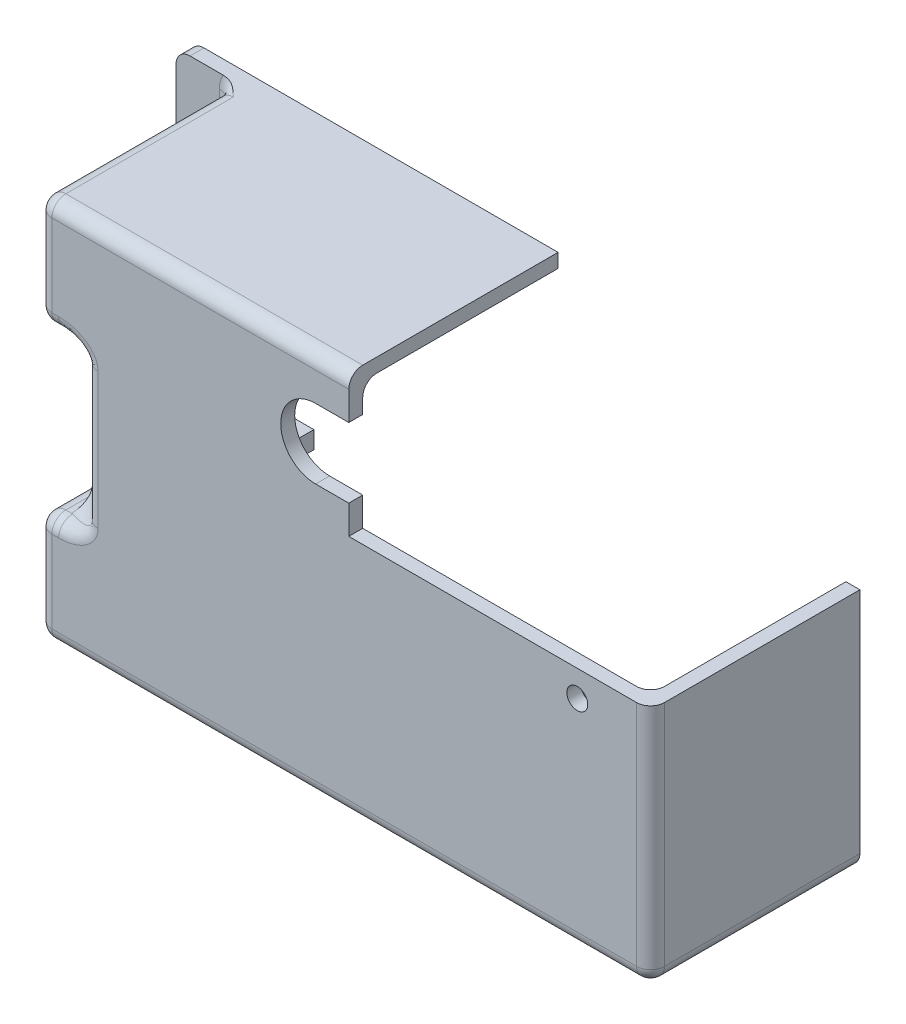
SolidWorks part; units mm, degrees
material "3D_printed_PLA"
ref_plane "Front Plane" through (0, 0, 0) normal (0, 0, 1) x (1, 0, 0)
ref_plane "Top Plane" through (0, 0, 0) normal (0, 1, 0) x (1, 0, 0)
ref_plane "Right Plane" through (0, 0, 0) normal (1, 0, 0) x (0, 0, -1)
sketch "Sketch1" plane through (0, 0, 0) normal (0, 0, 1) x (1, 0, 0)
  line L1 (-48, -27.5) -> (48, -27.5)
  line L2 (-48, -27.5) -> (-48, 27.5)
  line L3 (-48, 27.5) -> (48, 27.5)
  line L4 (48, -27.5) -> (48, 27.5)
  line L5 (-48, -27.5) -> (48, 27.5) construction
  line L6 (-48, 27.5) -> (48, -27.5) construction
  point P0 (0, 0)
  dimension "D1" = 96
  dimension "D2" = 55
extrude "Boss-Extrude1" add sketch "Sketch1" along normal blind 2
sketch "Sketch2" plane through (0, 0, 0) normal (0, 0, -1) x (-1, 0, 0)
  line L0 (-46, 25.5) -> (-46, -25.5)
  line L1 (-46, -25.5) -> (46, -25.5)
  line L2 (46, -25.5) -> (46, 25.5)
  line L3 (46, 25.5) -> (-46, 25.5)
  line L4 (-48, 27.5) -> (-48, -27.5)
  line L5 (-48, -27.5) -> (48, -27.5)
  line L6 (48, -27.5) -> (48, 27.5)
  line L7 (48, 27.5) -> (-48, 27.5)
  line L8 (-48, 27.5) -> (-48, -27.5)
  line L9 (-48, -27.5) -> (48, -27.5)
  line L10 (48, -27.5) -> (48, 27.5)
  line L11 (48, 27.5) -> (-48, 27.5)
  dimension "D1" = 0
  dimension "D2" = 2
extrude "Boss-Extrude2" add sketch "Sketch2" along normal blind 28
sketch "Sketch5" plane through (0, 0, 2) normal (0, 0, 1) x (1, 0, 0)
  line L0 (-48, 11.75) -> (-30, 11.75)
  line L1 (-48, 27.5) -> (-48, -27.5) construction
  line L2 (-30, 11.75) -> (-30, 14.25)
  line L3 (-30, 14.25) -> (-39, 14.25)
  line L4 (-39, 14.25) -> (-39, 27.5)
  line L5 (48, 27.5) -> (-48, 27.5) construction
  line L6 (-39, 27.5) -> (-48, 27.5)
  line L7 (-48, 27.5) -> (-48, 11.75)
  line L8 (-46, 0) -> (-39.8001, 0) construction
  line L9 (-46, -25.5) -> (-46, 25.5) construction
  line L10 (-39, -27.5) -> (-48, -27.5)
  line L11 (-39, -14.25) -> (-39, -27.5)
  line L12 (-30, -14.25) -> (-39, -14.25)
  line L13 (-30, -11.75) -> (-30, -14.25)
  line L14 (-48, -11.75) -> (-30, -11.75)
  line L15 (-48, -27.5) -> (-48, -11.75)
  dimension "D1" = 15.75
  dimension "D2" = 18
  dimension "D3" = 2.5
  dimension "D4" = 9
extrude "Boss-Extrude3" add sketch "Sketch5" against normal offset from surface (29.75 mm away) 0.25 up to face at (0, 0, -28)
sketch "Sketch6" plane through (0, 0, 2) normal (0, 0, 1) x (1, 0, 0)
  line L0 (-46, -11.75) -> (-30, -11.75) construction
  line L1 (-30, 11.75) -> (-37, 11.75)
  line L2 (-30, 11.75) -> (-30, -11.75)
  line L3 (-30, -11.75) -> (-37, -11.75)
  line L4 (-37, 11.75) -> (-37, -11.75)
  dimension "D1" = 7
extrude "Boss-Extrude4" add sketch "Sketch6" against normal blind 5.75
sketch "Sketch7" plane through (-48, 0, 0) normal (-1, 0, 0) x (0, 0, 1)
  line L0 (2, 27.5) -> (2, -27.5) construction
  line L1 (2, -11.75) -> (-28, -11.75)
  line L2 (2, -11.75) -> (2, 11.75)
  line L3 (2, 11.75) -> (-28, 11.75)
  line L4 (-28, -11.75) -> (-28, 11.75)
  line L5 (-28, -27.5) -> (-28, 27.5) construction
  line L6 (-28, 27.5) -> (2, 0) construction
  line L7 (2, 0) -> (-28, -27.5) construction
  line L8 (0, 11.75) -> (-27.75, 11.75) construction
extrude "Cut-Extrude2" cut sketch "Sketch7" against normal up to vertex
sketch "Sketch8" plane through (0, -27.5, 0) normal (0, -1, 0) x (1, 0, 0)
  line L0 (48, -28) -> (-48, -28) construction
  line L1 (-48, 2) -> (-39.8, 2)
  line L2 (-48, 2) -> (-48, -26)
  line L3 (-48, -26) -> (-39.8, -26)
  line L4 (-39.8, 2) -> (-39.8, -26)
  line L5 (-39, 0) -> (-39, -27.75) construction
  dimension "D1" = 2
  dimension "D2" = 0.8
extrude "Cut-Extrude3" cut sketch "Sketch8" against normal through all both and the other way through all
chamfer "Chamfer1" distance 5 angle 45 1 edges at (-37, 0, 2)
fillet "Fillet1" radius 2 32 edges at (3.5, -25.5, 0) (46, 0, 0) (3.5, 25.5, 0) (4.1, -27.5, 2) (4.1, 27.5, 2) (48, 0, 2) (-46, 25.5, -27.875) (-46, -25.5, -27.875) (46, -25.5, -14) (46, 25.5, -14) (-48, 27.5, -27) (48, 27.5, -13) (48, -27.5, -13) (-48, -27.5, -27) (-39, -19.875, 0) (-39, 19.875, 0) (-34.5, 14.25, 0) (-30, 0, 0) (-34.5, -14.25, 0) (-39.8, 19.625, 2) (-39.8, -19.625, 2) (-35.9, -11.75, 2) (-32, 0, 2) (-35.9, 11.75, 2) (-48, -11.75, -27) (-48, 11.75, -27) (-39.8, 11.75, -12) (-39.8, -11.75, -12) (-34.5, -11.75, -0.5) (-34.5, 11.75, -0.5) (-39.8, -27.5, -12) (-39.8, 27.5, -12)
sketch "Sketch3" plane through (0, 0, 2) normal (0, 0, 1) x (1, 0, 0)
  line L0 (48, 25.5) -> (48, -25.5) construction
  line L1 (48, 7.25) -> (4.75, 7.25)
  line L2 (48, 7.25) -> (48, 27.5)
  line L3 (48, 27.5) -> (4.75, 27.5)
  line L4 (4.75, 7.25) -> (4.75, 27.5)
  line L5 (-37.8, 27.5) -> (46, 27.5) construction
  dimension "D1" = 43.25
  dimension "D2" = 20.25
extrude "Cut-Extrude1" cut sketch "Sketch3" against normal through all both and the other way through all
fillet "Fillet2" radius 2 6 edges at (-39.2142, -12.3358, -26) (-39.2142, -26.9142, -26) (-39.2142, 26.9142, -26) (-39.2142, 12.3358, -26) (-39.8, -19.625, -26) (-39.8, 19.625, -26)
sketch "Sketch9" plane through (0, 0, -26) normal (0, 0, 1) x (1, 0, 0)
  circle A0 centre (-42.5, -18.75) radius 3
  circle A1 centre (-42.5, 18.75) radius 3
  dimension "D1" = 6
extrude "Cut-Extrude4" cut sketch "Sketch9" along normal through all
sketch "Sketch10" plane through (0, 0, -26) normal (0, 0, 1) x (1, 0, 0)
  circle A0 centre (-42.5, 18.75) radius 1.5
  circle A1 centre (-42.5, -18.75) radius 1.5
  dimension "D1" = 3
extrude "Cut-Extrude5" cut sketch "Sketch10" against normal through all
sketch "Sketch11" plane through (0, 0, 2) normal (0, 0, 1) x (1, 0, 0)
  circle A0 centre (37.5, 3.5) radius 1.5 construction
  circle A1 centre (37.5, 3.5) radius 1.5
extrude "Cut-Extrude6" cut sketch "Sketch11" against normal through all both and the other way through all
sketch "Sketch12" plane through (0, 0, 2) normal (0, 0, 1) x (1, 0, 0)
  line L0 (4.75, 16.375) -> (0, 16.375) construction
  line L1 (4.75, 7.25) -> (4.75, 25.5) construction
  line L2 (4.75, 11.375) -> (0, 11.375)
  line L3 (4.75, 21.375) -> (0, 21.375)
  arc A0 (4.75, 11.375) -> (4.75, 21.375) centre (4.75, 16.375) ccw
  arc A1 (0, 21.375) -> (0, 11.375) centre (0, 16.375) ccw
  point P4 (2.375, 16.375)
  dimension "D1" = 5
extrude "Cut-Extrude7" cut sketch "Sketch12" against normal through all both and the other way through all
